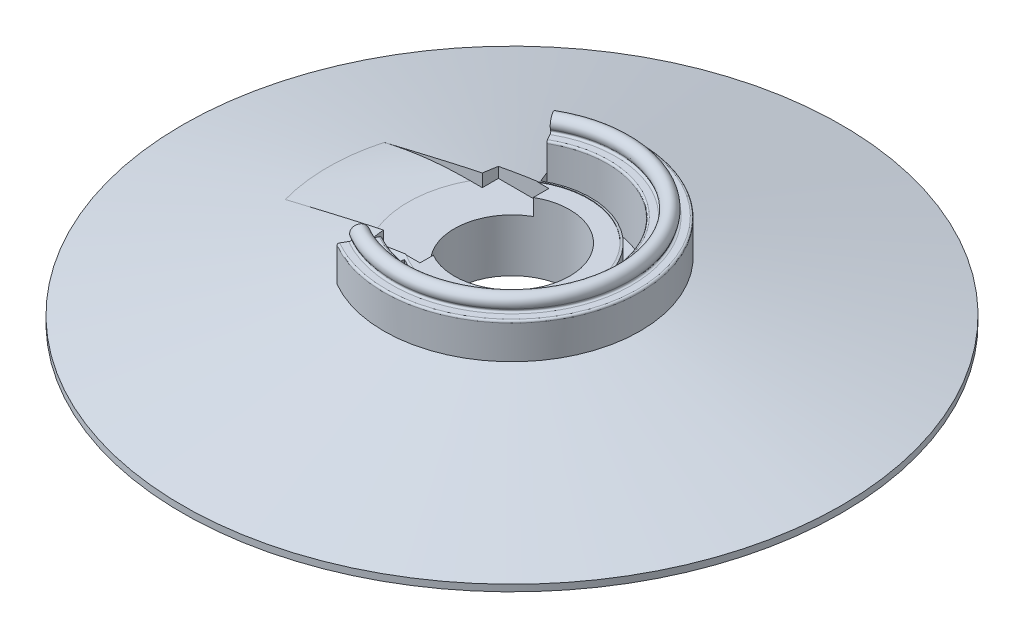
SolidWorks part; units mm, degrees
ref_plane "Alzado" through (0, 0, 0) normal (0, 0, 1) x (1, 0, 0)
ref_plane "Planta" through (0, 0, 0) normal (0, 1, 0) x (1, 0, 0)
ref_plane "Vista lateral" through (0, 0, 0) normal (1, 0, 0) x (0, 0, -1)
sketch "Croquis1" plane through (0, 0, 0) normal (0, 0, 1) x (1, 0, 0)
  line L0 (-11.6, -8.5) -> (-8.8493, -8.5)
  line L2 (-11.6, -7.5) -> (-11.6, 7.5)
  line L7 (-11.6, 8.5) -> (-8.8493, 8.5)
  line L8 (-8.8493, -8.5) -> (-7.8937, -8.5)
  line L9 (-8.8493, 8.5) -> (-7.8937, 8.5)
  line L10 (-11.6, 8.5) -> (-11.6, 7.5)
  line L11 (-11.6, -8.5) -> (-11.6, -7.5)
  arc A0 (-7.8937, -8.5) -> (-7.8937, 8.5) centre (0, 0) ccw
extrude "Saliente-Extruir1" add sketch "Croquis1" along normal blind 3
sketch "Croquis2" plane through (0, 0, 0) normal (0, 0, -1) x (-1, 0, 0)
  line L6 (7.8937, -8.5) -> (11.6, -8.5)
  line L7 (11.6, -8.5) -> (11.6, 8.5)
  line L8 (11.6, 8.5) -> (7.8937, 8.5)
  line L9 (7.8937, -8.5) -> (11.6, -8.5)
  line L10 (11.6, -8.5) -> (11.6, 8.5)
  line L11 (11.6, 8.5) -> (7.8937, 8.5)
  circle A0 centre (0, 0) radius 8.7491
  arc A3 (7.8937, 8.5) -> (7.8937, -8.5) centre (0, 0) ccw
  arc A4 (7.8937, 8.5) -> (7.8937, -8.5) centre (0, 0) ccw
  dimension "D1" = 0
extrude "Saliente-Extruir2" add sketch "Croquis2" along normal up to surface (5.5 mm away)
sketch "Croquis3" plane through (0, 0, 3) normal (0, 0, 1) x (1, 0, 0)
  circle A0 centre (0, 0) radius 50
extrude "Saliente-Extruir3" add sketch "Croquis3" along normal blind 2
sketch "Croquis5" plane through (0, 0, 3) normal (0, 0, -1) x (-1, 0, 0)
  line L6 (7.8937, -8.5) -> (11.6, -8.5)
  line L7 (11.6, -8.5) -> (11.6, 8.5)
  line L8 (11.6, 8.5) -> (7.8937, 8.5)
  line L9 (7.8937, -8.5) -> (11.6, -8.5)
  line L10 (11.6, -8.5) -> (11.6, 8.5)
  line L11 (11.6, 8.5) -> (7.8937, 8.5)
  circle A0 centre (0, 0) radius 50
  circle A1 centre (0, 0) radius 50
  arc A4 (7.8937, 8.5) -> (7.8937, -8.5) centre (0, 0) ccw
  arc A5 (7.8937, 8.5) -> (7.8937, -8.5) centre (0, 0) ccw
  circle M6 centre (0, 0) radius 50
  line M7 (7.8937, 8.5) -> (11.6, 8.5)
  line M8 (11.6, 8.5) -> (11.6, -8.5)
  line M9 (11.6, -8.5) -> (7.8937, -8.5)
  arc M10 (7.8937, -8.5) -> (7.8937, 8.5) centre (0, 0) cw
  dimension "D1" = 0
  dimension "D2" = 0
extrude "Saliente-Extruir4" add sketch "Croquis5" along normal blind 9 contours M6 M10 M7 M8 M9 region at (48.5858, 0, 3)
chamfer "Chaflán1" distance 10 angle 76 1 edges at (-50, 0, -6) first distance on face at (50, 0, 5)
sketch "Croquis7" plane through (0, 0, -5.5) normal (0, 0, -1) x (-1, 0, 0)
  line L0 (4.2083, -7.5) -> (11.6, -7.5) construction
  line L1 (2.914, -7.5) -> (37.7017, -7.5)
  line L2 (2.914, -7.5) -> (2.914, 7.5)
  line L3 (2.914, 7.5) -> (37.7017, 7.5)
  line L4 (37.7017, -7.5) -> (37.7017, 7.5)
extrude "Cortar-Extruir1" cut sketch "Croquis7" against normal blind 2.5 and the other way blind 5
sketch "Croquis8" plane through (0, 0, -5.5) normal (0, 0, -1) x (-1, 0, 0)
  line L0 (0, 0) -> (14, 0) construction
  line L1 (5.9676, 10.3362) -> (7.2176, 12.5013)
  line L2 (5.9676, -10.3362) -> (7.2176, -12.5013)
  arc A0 (5.9676, 10.3362) -> (5.9676, -10.3362) centre (0, 0) ccw
  arc A1 (7.2176, 12.5013) -> (7.2176, -12.5013) centre (0, 0) ccw
extrude "Cortar-Extruir9" cut sketch "Croquis8" against normal blind 5
sketch "Croquis9" plane through (0, 0, 5) normal (0, 0, 1) x (1, 0, 0)
  line L0 (-7.2176, -12.5013) -> (-9.7176, -16.8314)
  line L1 (-7.2176, 12.5013) -> (-9.7176, 16.8314)
  arc A3 (-9.7176, -16.8314) -> (-9.7176, 16.8314) centre (0, 0) ccw
  arc A4 (-7.2176, -12.5013) -> (-7.2176, 12.5013) centre (0, 0) ccw
  arc A5 (-7.2176, -12.5013) -> (-7.2176, 12.5013) centre (0, 0) ccw
  point P14 (0, 0)
  dimension "D1" = 0
extrude "Saliente-Extruir5" add sketch "Croquis9" against normal blind 14
move or copy body "Sólido-Mover/Copiar3" bodies to move or copy 108 copy no translate (-26.9128, 15.9547, 13.3361) parameters "D1"=0, "D2"=0, "D3"=0
move or copy body "Sólido-Mover/Copiar4" bodies to move or copy 109 copy no rotation origin (0, 0, 0) rotation axis (1, 0, 0) rotation angle 90
sketch "Croquis10" plane through (-27.0932, 0, 15.6423) normal (-0.866, 0, 0.5) x (0.5, 0, 0.866)
  line L0 (-16.5745, -4.3361) -> (-16.5745, -4.4361) construction
  line L1 (-19.0745, -4.3361) -> (-14.0745, -4.3361) construction
  line L2 (-14.0745, -4.3361) -> (-19.0745, -4.3361) construction
  line L3 (-16.5745, -4.3361) -> (-16.5745, -3.3361) construction
  circle A1 centre (-16.5745, -3.3361) radius 1.1
  point P2 (-16.5745, -3.3361)
ref_plane "Plano1" through (0, -3.3361, 0) normal (0, 1, 0) x (1, 0, 0)
sketch "Croquis11" plane through (0, -3.3361, 0) normal (0, 1, 0) x (1, 0, 0)
  line L0 (-34.1304, -28.456) -> (-36.6304, -32.7861) construction
  arc A0 (-35.3804, -1.2883) -> (-35.3804, -30.6211) centre (-26.9128, -15.9547) cw
sweep "Barrer1" add profiles "Croquis10" path "Croquis11"
fillet "Redondeo1" radius 0.3 4 edges at (-9.5193, -4.3361, 15.9547) (-10.4358, -4.3361, 15.9547) (-7.4775, -4.3361, 15.9547) (-12.4775, -4.3361, 15.9547) conic rho 0.5
fillet "Redondeo2" radius 50.3 1 edges at (-48.8373, -10.3361, 15.9547)
sketch "Croquis12" plane through (0, -7.8361, 0) normal (0, 1, 0) x (1, 0, 0)
  line L1 (-38.9187, -6.0107) -> (-31.2646, -6.0107)
  line L2 (-38.9187, -6.0107) -> (-38.9187, -25.5628)
  line L3 (-38.9187, -25.5628) -> (-31.2646, -25.5628)
  line L4 (-31.2646, -6.0107) -> (-31.2646, -25.5628)
extrude "Cortar-Extruir10" cut sketch "Croquis12" against normal up to surface (2.5 mm away) and the other way blind 5 up to face at (-37.6255, -10.3361, 15.9547)
sketch "Croquis13" plane through (0, -13.3361, 0) normal (0, 1, 0) x (1, 0, 0)
  circle A2 centre (-26.9128, -15.9547) radius 8.7491
  circle A3 centre (-26.9128, -15.9547) radius 8.7491
  dimension "D1" = 0
extrude "Cortar-Extruir11" cut sketch "Croquis13" against normal blind 10
